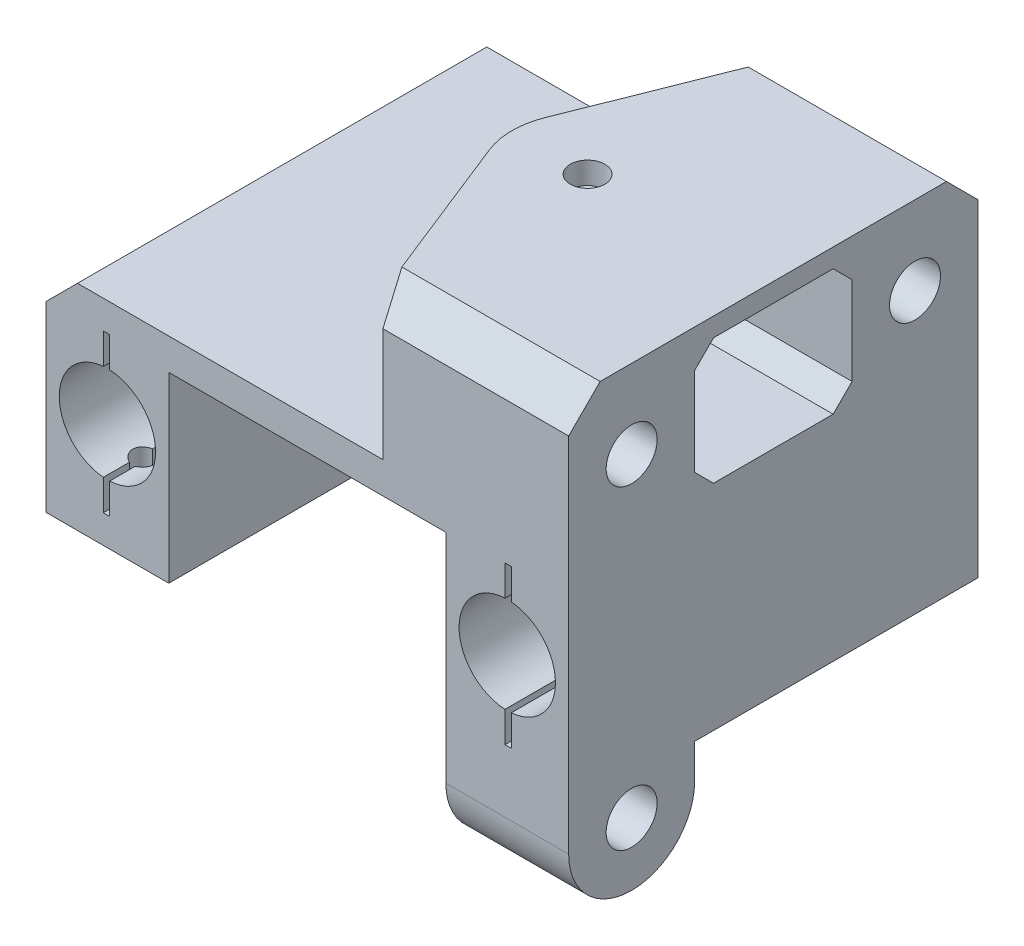
SolidWorks part; units mm, degrees
ref_plane "Front Plane" through (0, 0, 0) normal (0, 0, 1) x (1, 0, 0)
ref_plane "Top Plane" through (0, 0, 0) normal (0, 1, 0) x (1, 0, 0)
ref_plane "Right Plane" through (0, 0, 0) normal (1, 0, 0) x (0, 0, -1)
sketch "Sketch1" plane through (0, 0, 0) normal (0, 0, 1) x (1, 0, 0)
  line L0 (31.75, 17) -> (-31.75, 17)
  line L1 (-22, -12) -> (22, -12)
  line L2 (-22, -12) -> (-22, 12)
  line L3 (-22, 12) -> (22, 12)
  line L4 (22, -12) -> (22, 12)
  line L5 (-22, -12) -> (22, 12) construction
  line L6 (-22, 12) -> (22, -12) construction
  line L7 (-31.75, -17) -> (31.75, -17)
  line L8 (31.75, -17) -> (41.5, -17)
  line L9 (41.5, 17) -> (31.75, 17)
  line L10 (-31.75, -17) -> (-41.5, -17)
  line L11 (-41.5, -17) -> (-41.5, 17)
  line L12 (0, 0) -> (0, 8.5) construction
  line L13 (41.5, -17) -> (41.5, 17)
  line L15 (-41.5, 17) -> (-31.75, 17)
  circle A0 centre (-31.75, 0) radius 7.65
  circle A1 centre (31.75, 0) radius 7.65
  point P0 (0, 0)
  point P8 (-22, 0)
  point P12 (22, 0)
  dimension "D3" = 15.3
  dimension "D5" = 15.3
  dimension "D1" = 44
  dimension "D2" = 24
  dimension "D4" = 9.75
  dimension "D6" = 9.75
  dimension "D7" = 5
  dimension "D8" = 5
  dimension "D9" = 9.75
extrude "Boss-Extrude1" add sketch "Sketch1" along normal blind 65
sketch "Sketch6" plane through (0, 12, 0) normal (0, -1, 0) x (-1, 0, 0)
  line L0 (0, -65) -> (0, 0) construction
  line L1 (-22, -65) -> (22, -65) construction
  line L2 (-22, 0) -> (22, 0) construction
  circle A0 centre (-12, -32.5) radius 2.75
  point P9 (0, -32.5)
  dimension "D1" = 5.5
  dimension "D2" = 12
  dimension "D3" = 0
extrude "Cut-Extrude1" cut sketch "Sketch6" against normal blind 15
ref_plane "Plane2" through (0, 37, 0) normal (0, 1, 0) x (1, 0, 0)
sketch "Sketch7" plane through (41.5, 0, 0) normal (1, 0, 0) x (0, 0, -1)
  line L0 (-55, -22.5) -> (-10, -22.5) construction
  line L1 (-10, -22.5) -> (-10, 22.5) construction
  line L2 (-65, 17) -> (0, 17) construction
  line L3 (0, -17) -> (0, 17) construction
  line L4 (-65, -17) -> (-65, -22.5)
  line L5 (-45, -22.5) -> (-45, -17)
  line L6 (-65, -17) -> (0, -17) construction
  line L7 (-45, -17) -> (-65, -17)
  arc A0 (-65, -22.5) -> (-45, -22.5) centre (-55, -22.5) ccw
  circle A1 centre (-55, -22.5) radius 4.05
  point P1 (-32.5, -22.5)
  point P7 (-32.5, 17)
  point P8 (-10, 0)
  point P11 (0, 0)
  dimension "D2" = 8.1
  dimension "D3" = 0
  dimension "D1" = 45
  dimension "D4" = 0
extrude "Boss-Extrude2" add sketch "Sketch7" against normal up to surface (83 mm away) up to face at (-41.5, 0, 32.5)
sketch "Sketch8" plane through (0, 0, 0) normal (0, 0, -1) x (-1, 0, 0)
  line L0 (41.5, -17) -> (22, -17)
  line L1 (22, -12) -> (-22, -12) construction
  line L2 (-22, -12) -> (22, -12)
  line L3 (-22, -12) -> (-22, -37.9987)
  line L4 (-22, -37.9987) -> (22, -37.9987)
  line L5 (22, -12) -> (22, -17)
  line L6 (41.5, -17) -> (-41.5, -17) construction
  line L7 (41.5, -17) -> (41.5, -37.9987)
  line L8 (41.5, -37.9987) -> (22, -37.9987)
  point P6 (0, -12)
  dimension "D1" = 0
  dimension "D2" = 44
extrude "Cut-Extrude2" cut sketch "Sketch8" against normal blind 86
sketch "Sketch9" plane through (41.5, 0, 0) normal (-1, 0, 0) x (0, 0, 1)
  line L0 (0, 17) -> (0, 37)
  line L1 (0, 37) -> (20, 37)
  line L2 (20, 37) -> (20, 17)
  line L3 (65, 17) -> (0, 17) construction
  line L4 (20, 17) -> (0, 17)
  line L5 (10, 27.5) -> (0, 27.5) construction
  line L6 (10, 27.5) -> (20, 27.5) construction
  line L8 (65, 17) -> (45, 17)
  line L9 (65, 17) -> (65, 37)
  line L10 (65, 37) -> (45, 37)
  line L11 (45, 17) -> (45, 37)
  circle A0 centre (10, 27.5) radius 4.05
  circle A1 centre (55, -22.5) radius 4.05 construction
  circle A2 centre (55, 27.5) radius 4.05
  dimension "D1" = 8.1
  dimension "D2" = 50
  dimension "D3" = 45
  dimension "D4" = 20
extrude "Boss-Extrude3" add sketch "Sketch9" along normal up to surface (19.5 mm away) up to face at (22, -10.8333, 36.6667)
sketch "Sketch10" plane through (0, 12, 0) normal (0, -1, 0) x (-1, 0, 0)
  line L1 (-7.6699, -32.5) -> (-9.8349, -28.75)
  line L2 (-9.8349, -28.75) -> (-14.1651, -28.75)
  line L3 (-14.1651, -28.75) -> (-16.3301, -32.5)
  line L4 (-16.3301, -32.5) -> (-14.1651, -36.25)
  line L5 (-14.1651, -36.25) -> (-9.8349, -36.25)
  line L6 (-9.8349, -36.25) -> (-7.6699, -32.5)
  circle A0 centre (-12, -32.5) radius 3.75 construction
  dimension "D1" = 7.5
extrude "Cut-Extrude3" cut sketch "Sketch10" against normal blind 3.5
chamfer "Chamfer3" distance 3 angle 45 2 edges at (31.75, 17, 45) (31.75, 17, 20)
chamfer "Chamfer4" distance 5 angle 45 1 edges at (-41.5, 17, 32.5)
sketch "Sketch11" plane through (0, 37, 0) normal (0, 1, 0) x (1, 0, 0)
  line L0 (22, -65) -> (2.514, -39.8495)
  line L1 (41.5, -65) -> (22, -65)
  line L2 (41.5, -65) -> (41.5, 0)
  line L3 (41.5, 0) -> (0, 0)
  line L5 (2.514, -25.1505) -> (22, 0)
  arc A0 (2.514, -25.1505) -> (2.514, -39.8495) centre (12, -32.5) ccw
  circle A1 centre (12, -32.5) radius 2.75
  line M3 (22, -45) -> (22, -65)
  line M4 (22, -65) -> (41.5, -65)
  line M5 (41.5, -65) -> (41.5, -45)
  line M6 (41.5, -45) -> (22, -45)
  dimension "D1" = 5.5
extrude "Boss-Extrude4" add sketch "Sketch11" along normal blind 3 contours M6 M3 M4 M5 | L5 A0 L0 L2 L3 M3 M6 region at (31.75, 37, 55) region at (23.3909, 37, 27.1993)
sketch "Sketch13" plane through (0, 0, 65) normal (0, 0, 1) x (1, 0, 0)
  line L0 (-31.8914, 12.5) -> (-31.8914, -12.5)
  circle A0 centre (-31.75, 0) radius 7.65 construction
  dimension "D1" = 25
  dimension "D2" = 12.5
extrude "Cut-Extrude-Thin1" cut sketch "Sketch13" against normal blind 77 and the other way through all thin thin type mid plane wall 1
mirror "Mirror2" about plane through (0, 0, 0) normal (1, 0, 0) of "Cut-Extrude-Thin1"
chamfer "Chamfer5" distance 3 angle 45 2 edges at (31.75, 37, 20) (31.75, 37, 45)
sketch "Sketch14" plane through (0, 17, 0) normal (0, 1, 0) x (1, 0, 0)
  circle A0 centre (12, -32.5) radius 2.75
  circle A1 centre (12, -32.5) radius 3
  dimension "D1" = 6
extrude "Boss-Extrude5" add sketch "Sketch14" along normal blind 0.5
chamfer "Chamfer8" distance 0.5 angle 45 1 edges at (15, 17, 32.5)
sketch "Sketch15" plane through (0, 37, 0) normal (0, -1, 0) x (-1, 0, 0)
  circle A0 centre (-12, -32.5) radius 2.75
  circle A1 centre (-12, -32.5) radius 3
  dimension "D1" = 6
extrude "Boss-Extrude6" add sketch "Sketch15" along normal blind 0.5
chamfer "Chamfer9" distance 0.5 angle 45 1 edges at (12, 37, 35.5)
sketch "Sketch16" plane through (22, 0, 0) normal (-1, 0, 0) x (0, 0, 1)
  line L6 (0, 37) -> (0, 17)
  line L7 (0, 17) -> (23, 17)
  line L8 (23, 17) -> (20, 20)
  line L9 (20, 20) -> (20, 34)
  line L10 (20, 34) -> (23, 37)
  line L11 (23, 37) -> (0, 37)
  line L12 (0, 37) -> (0, 17)
  line L13 (0, 17) -> (23, 17)
  line L14 (23, 17) -> (20, 20)
  line L15 (20, 20) -> (20, 34)
  line L16 (20, 34) -> (23, 37)
  line L17 (23, 37) -> (0, 37)
  line L18 (42, 17) -> (65, 17)
  line L19 (65, 17) -> (65, 37)
  line L20 (65, 37) -> (42, 37)
  line L21 (42, 37) -> (45, 34)
  line L22 (45, 34) -> (45, 20)
  line L23 (45, 20) -> (42, 17)
  line L24 (42, 17) -> (65, 17)
  line L25 (65, 17) -> (65, 37)
  line L26 (65, 37) -> (42, 37)
  line L27 (42, 37) -> (45, 34)
  line L28 (45, 34) -> (45, 20)
  line L29 (45, 20) -> (42, 17)
  circle A0 centre (10, 27.5) radius 4.05
  circle A1 centre (55, 27.5) radius 4.05
  dimension "D1" = 0
  dimension "D2" = 0
extrude "Boss-Extrude7" add sketch "Sketch16" along normal blind 10
sketch "Sketch17" plane through (0, 37, 0) normal (0, 1, 0) x (1, 0, 0)
  line L0 (22, 0) -> (12, 0)
  line L1 (0.8479, -28.0692) -> (12, 0)
  line L2 (22, 0) -> (12, -20.5)
  arc A0 (12, -20.5) -> (0.8479, -28.0692) centre (12, -32.5) ccw
extrude "Boss-Extrude8" add sketch "Sketch17" along normal blind 3
sketch "Sketch18" plane through (0, -17, 0) normal (0, -1, 0) x (-1, 0, 0)
  line L0 (31.75, 0) -> (31.75, -65) construction
  line L1 (41.5, 0) -> (22, 0) construction
  line L2 (41.5, -65) -> (22, -65) construction
  line L3 (-31.75, 0) -> (-31.75, -40) construction
  line L4 (-22, 0) -> (-41.5, 0) construction
  circle A0 centre (31.75, -6) radius 1.95
  circle A1 centre (-31.75, -6) radius 1.95
  circle A2 centre (31.75, -59) radius 1.95
  circle A3 centre (-31.75, -32.5) radius 1.95
  dimension "D1" = 3.9
  dimension "D2" = 6
  dimension "D3" = 6
  dimension "D4" = 6
  dimension "D5" = 26.5
extrude "Cut-Extrude4" cut sketch "Sketch18" against normal blind 16
ref_plane "Plane3" through (0, 0, 32.5) normal (0, 0, 1) x (1, 0, 0)
mirror "Mirror3" about plane through (0, 0, 32.5) normal (0, 0, 1) of "Boss-Extrude8"
chamfer "Chamfer10" distance 5 angle 45 2 edges at (26.75, 40, 65) (26.75, 40, 0)
chamfer "Chamfer11" distance 2 angle 45 2 edges at (12, 37, 52.5) (12, 37, 12.5)
sketch "Sketch19" plane through (0, 0, 32.5) normal (0, 0, 1) x (1, 0, 0)
  line L0 (33.7, -7.3973) -> (29.8, -7.3973)
  line L1 (32.3914, 7.6231) -> (31.3914, 7.6416)
  arc A0 (31.3914, 7.6416) -> (29.8, -7.3973) centre (31.75, 0) ccw
  arc A1 (31.3914, 7.6416) -> (29.8, -7.3973) centre (31.75, 0) ccw
  arc A2 (33.7, -7.3973) -> (32.3914, 7.6231) centre (31.75, 0) ccw
  arc A3 (33.7, -7.3973) -> (32.3914, 7.6231) centre (31.75, 0) ccw
  circle A4 centre (31.75, 0) radius 5
  dimension "D1" = 10
extrude "Boss-Extrude9" add sketch "Sketch19" along normal offset from surface 24 and the other way offset from surface 24 up to face at (-1.1364, 5.5455, 65) other way up to face at (-1.1364, 6.5455, 0)
mirror "Mirror4" about plane through (0, 0, 0) normal (1, 0, 0) of "Boss-Extrude9"
sketch "Sketch20" plane through (41.5, 0, 0) normal (1, 0, 0) x (0, 0, -1)
  line L7 (-5, 40) -> (-60, 40)
  line L8 (-60, 40) -> (-65, 35)
  line L9 (-65, 35) -> (-65, -22.5)
  line L10 (-45, -22.5) -> (-45, -17)
  line L11 (-45, -17) -> (0, -17)
  line L12 (0, -17) -> (0, 35)
  line L13 (0, 35) -> (-5, 40)
  line L14 (-5, 40) -> (-60, 40)
  line L15 (-60, 40) -> (-65, 35)
  line L16 (-65, 35) -> (-65, -22.5)
  line L17 (-45, -22.5) -> (-45, -17)
  line L18 (-45, -17) -> (0, -17)
  line L19 (0, -17) -> (0, 35)
  line L20 (0, 35) -> (-5, 40)
  line L37 (-45, 34) -> (-45, 20)
  line L38 (-42, 37) -> (-45, 34)
  line L39 (-23, 37) -> (-42, 37)
  line L40 (-20, 34) -> (-23, 37)
  line L41 (-20, 20) -> (-20, 34)
  line L42 (-23, 17) -> (-20, 20)
  line L43 (-42, 17) -> (-23, 17)
  line L44 (-45, 20) -> (-42, 17)
  line L45 (-45, 34) -> (-45, 20)
  line L46 (-42, 37) -> (-45, 34)
  line L47 (-23, 37) -> (-42, 37)
  line L48 (-20, 34) -> (-23, 37)
  line L49 (-20, 20) -> (-20, 34)
  line L50 (-23, 17) -> (-20, 20)
  line L51 (-42, 17) -> (-23, 17)
  line L52 (-45, 20) -> (-42, 17)
  arc A1 (-65, -22.5) -> (-45, -22.5) centre (-55, -22.5) ccw
  arc A2 (-65, -22.5) -> (-45, -22.5) centre (-55, -22.5) ccw
  circle A7 centre (-55, 27.5) radius 4.05
  circle A8 centre (-55, 27.5) radius 4.05
  circle A9 centre (-10, 27.5) radius 4.05
  circle A10 centre (-10, 27.5) radius 4.05
  circle A11 centre (-55, -22.5) radius 4.05
  circle A12 centre (-55, -22.5) radius 4.05
  dimension "D1" = 0
  dimension "D2" = 0
  dimension "D3" = 0
  dimension "D4" = 0
  dimension "D5" = 0
